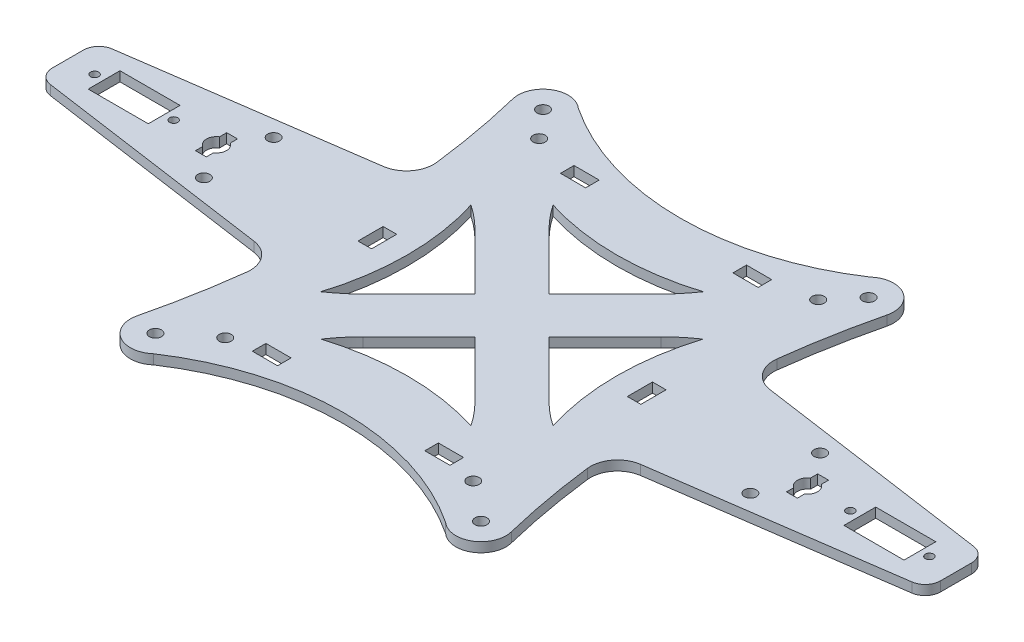
SolidWorks part; units mm, degrees
material "Thornel VCB-20 碳布"
ref_plane "前视基准面" through (0, 0, 0) normal (0, 0, 1) x (1, 0, 0)
ref_plane "上视基准面" through (0, 0, 0) normal (0, 1, 0) x (1, 0, 0)
ref_plane "右视基准面" through (0, 0, 0) normal (1, 0, 0) x (0, 0, -1)
sketch "草图1" plane through (0, 0, 0) normal (0, 1, 0) x (1, 0, 0)
  line L3 (-133.7177, 0) -> (146.3754, 0) construction
  line L56 (0, 96.0639) -> (0, -115.1457) construction
  line L65 (-25.5, 41.5) -> (-19, 41.5)
  line L66 (-36.5, 3.25) -> (-33, 3.25)
  line L70 (-36.5, 3.25) -> (-36.5, -3.25)
  line L76 (-36.5, -3.25) -> (-33, -3.25)
  line L80 (-33, 3.25) -> (-33, -3.25)
  line L81 (-25.5, -38) -> (-19, -38)
  line L82 (-25.5, -38) -> (-25.5, -41.5)
  line L83 (-25.5, -41.5) -> (-19, -41.5)
  line L84 (-19, -38) -> (-19, -41.5)
  line L85 (-19, 38) -> (-19, 41.5)
  line L86 (-25.5, 38) -> (-19, 38)
  line L142 (-25.5, 38) -> (-25.5, 41.5)
  line L143 (25.5, 38) -> (25.5, 41.5)
  line L144 (25.5, 38) -> (19, 38)
  line L145 (19, 38) -> (19, 41.5)
  line L146 (19, -38) -> (19, -41.5)
  line L147 (25.5, -41.5) -> (19, -41.5)
  line L148 (25.5, -38) -> (25.5, -41.5)
  line L149 (25.5, -38) -> (19, -38)
  line L150 (33, 3.25) -> (33, -3.25)
  line L151 (36.5, -3.25) -> (33, -3.25)
  line L152 (36.5, 3.25) -> (36.5, -3.25)
  line L153 (36.5, 3.25) -> (33, 3.25)
  line L154 (25.5, 41.5) -> (19, 41.5)
  line L155 (77.65, -2.1768) -> (77.65, -4.025)
  line L156 (74.85, 4.025) -> (77.65, 4.025)
  line L157 (74.85, 4.025) -> (74.85, 2.1768)
  line L158 (74.85, -4.025) -> (77.65, -4.025)
  line L159 (77.65, 4.025) -> (77.65, 2.1768)
  line L160 (74.85, -2.1768) -> (74.85, -4.025)
  line L161 (97.5, 7.6653) -> (97.5, -9.1503) construction
  line L162 (89.75, 4.1) -> (105.25, 4.1)
  line L163 (89.75, 4.1) -> (89.75, -4.1)
  line L164 (89.75, -4.1) -> (105.25, -4.1)
  line L165 (105.25, 4.1) -> (105.25, -4.1)
  line L166 (-97.5, 7.6653) -> (-97.5, -9.1503) construction
  line L167 (-105.25, 4.1) -> (-105.25, -4.1)
  line L168 (-89.75, -4.1) -> (-105.25, -4.1)
  line L169 (-89.75, 4.1) -> (-89.75, -4.1)
  line L170 (-89.75, 4.1) -> (-105.25, 4.1)
  line L171 (-74.85, -2.1768) -> (-74.85, -4.025)
  line L172 (-77.65, 4.025) -> (-77.65, 2.1768)
  line L173 (-74.85, -4.025) -> (-77.65, -4.025)
  line L174 (-74.85, 4.025) -> (-74.85, 2.1768)
  line L175 (-74.85, 4.025) -> (-77.65, 4.025)
  line L176 (-77.65, -2.1768) -> (-77.65, -4.025)
  line L177 (114.5911, 7.4683) -> (114.5911, -7.4683)
  line L178 (114.5911, 7.4683) -> (43.1936, 17.6463)
  line L179 (114.5911, -7.4683) -> (43.1936, -17.6463)
  line L180 (-114.5911, -7.4683) -> (-43.1936, -17.6463)
  line L181 (-114.5911, 7.4683) -> (-114.5911, -7.4683)
  line L182 (-114.5911, 7.4683) -> (-43.1936, 17.6463)
  line L183 (-23.978, 14.4296) -> (-9.5485, 0)
  line L184 (14.4296, 23.978) -> (0, 9.5485)
  line L185 (-23.978, -14.4296) -> (-9.5485, 0)
  line L186 (-14.4296, 23.978) -> (0, 9.5485)
  line L187 (23.978, -14.4296) -> (9.5485, 0)
  line L188 (23.978, 14.4296) -> (9.5485, 0)
  line L189 (-14.4296, -23.978) -> (0, -9.5485)
  line L190 (14.4296, -23.978) -> (0, -9.5485)
  circle A0 centre (-36, 43) radius 1.55
  circle A1 centre (-32, -42) radius 1.55
  circle A2 centre (32, -42) radius 1.55
  circle A3 centre (36, 43) radius 1.55
  circle A4 centre (42, 50) radius 1.55
  circle A5 centre (42, -50) radius 1.55
  circle A6 centre (-42, -50) radius 1.55
  circle A7 centre (-42, 50) radius 1.55
  arc A8 (74.85, 2.1768) -> (74.85, -2.1768) centre (76.25, 0) ccw
  arc A9 (77.65, -2.1768) -> (77.65, 2.1768) centre (76.25, 0) ccw
  circle A10 centre (107.7, 0) radius 1.05
  circle A11 centre (87.3, 0) radius 1.05
  circle A12 centre (-87.3, 0) radius 1.05
  circle A13 centre (-107.7, 0) radius 1.05
  arc A14 (-77.65, -2.1768) -> (-77.65, 2.1768) centre (-76.25, 0) cw
  arc A15 (-74.85, 2.1768) -> (-74.85, -2.1768) centre (-76.25, 0) cw
  arc A18 (-37.7098, 54.831) -> (37.7098, 54.831) centre (0, 111.5317) ccw
  arc A20 (48.2756, 48.4632) -> (43.1936, 17.6463) centre (246.1791, 0) ccw
  arc A21 (48.2756, 48.4632) -> (37.7098, 54.831) centre (42, 50) ccw
  arc A22 (-37.7098, -54.831) -> (37.7098, -54.831) centre (0, -111.5317) cw
  arc A23 (48.2756, -48.4632) -> (43.1936, -17.6463) centre (246.1791, 0) cw
  arc A24 (48.2756, -48.4632) -> (37.7098, -54.831) centre (42, -50) cw
  arc A26 (-48.2756, -48.4632) -> (-37.7098, -54.831) centre (-42, -50) ccw
  arc A27 (-48.2756, -48.4632) -> (-43.1936, -17.6463) centre (-246.1791, 0) ccw
  arc A28 (-48.2756, 48.4632) -> (-37.7098, 54.831) centre (-42, 50) cw
  arc A30 (-48.2756, 48.4632) -> (-43.1936, 17.6463) centre (-246.1791, 0) cw
  arc A31 (-23.978, 14.4296) -> (-29.9602, 19.3706) centre (-52.8883, -14.4807) ccw
  arc A32 (-23.978, -14.4296) -> (-29.9602, -19.3706) centre (-52.8883, 14.4807) cw
  arc A33 (-29.9602, -19.3706) -> (-29.9602, 19.3706) centre (-91.9966, 0) ccw
  arc A34 (-14.4296, 23.978) -> (-19.3706, 29.9602) centre (14.4807, 52.8883) cw
  arc A35 (-19.3706, 29.9602) -> (19.3706, 29.9602) centre (0, 91.9966) ccw
  arc A36 (14.4296, 23.978) -> (19.3706, 29.9602) centre (-14.4807, 52.8883) ccw
  arc A37 (23.978, 14.4296) -> (29.9602, 19.3706) centre (52.8883, -14.4807) cw
  arc A38 (29.9602, 19.3706) -> (29.9602, -19.3706) centre (91.9966, 0) ccw
  arc A39 (23.978, -14.4296) -> (29.9602, -19.3706) centre (52.8883, 14.4807) ccw
  arc A40 (14.4296, -23.978) -> (19.3706, -29.9602) centre (-14.4807, -52.8883) cw
  arc A41 (19.3706, -29.9602) -> (-19.3706, -29.9602) centre (0, -91.9966) ccw
  arc A42 (-14.4296, -23.978) -> (-19.3706, -29.9602) centre (14.4807, -52.8883) ccw
  circle A43 centre (70.5, 9) radius 1.55
  circle A44 centre (70.5, -9) radius 1.55
  circle A45 centre (-70.5, -9) radius 1.55
  circle A46 centre (-70.5, 9) radius 1.55
  point P118 (0, 0)
  dimension "D5" = 38
  dimension "D18" = 8.2
  dimension "D6" = 3.1
  dimension "D11" = 50
  dimension "D15" = 74.85
  dimension "D16" = 2.1
  dimension "D17" = 15.5
  dimension "D21" = 3.1
  dimension "D1" = 6.5
  dimension "D2" = 3.5
  dimension "D3" = 33
  dimension "D4" = 19
  dimension "D7" = 32
  dimension "D8" = 42
  dimension "D9" = 43
  dimension "D10" = 36
  dimension "D12" = 42
  dimension "D13" = 2.8
  dimension "D14" = 4
  dimension "D19" = 2.45
  dimension "D20" = 97.5
  dimension "D22" = 9
  dimension "D23" = 70.5
extrude "凸台-拉伸1" add sketch "草图1" along normal blind 2.5
fillet "圆角1" radius 4 4 edges at (114.5911, 1.25, -7.4683) (114.5911, 1.25, 7.4683) (-114.5911, 1.25, -7.4683) (-114.5911, 1.25, 7.4683)
fillet "圆角2" radius 7 4 edges at (-43.1936, 1.25, -17.6463) (43.1936, 1.25, -17.6463) (43.1936, 1.25, 17.6463) (-43.1936, 1.25, 17.6463)
